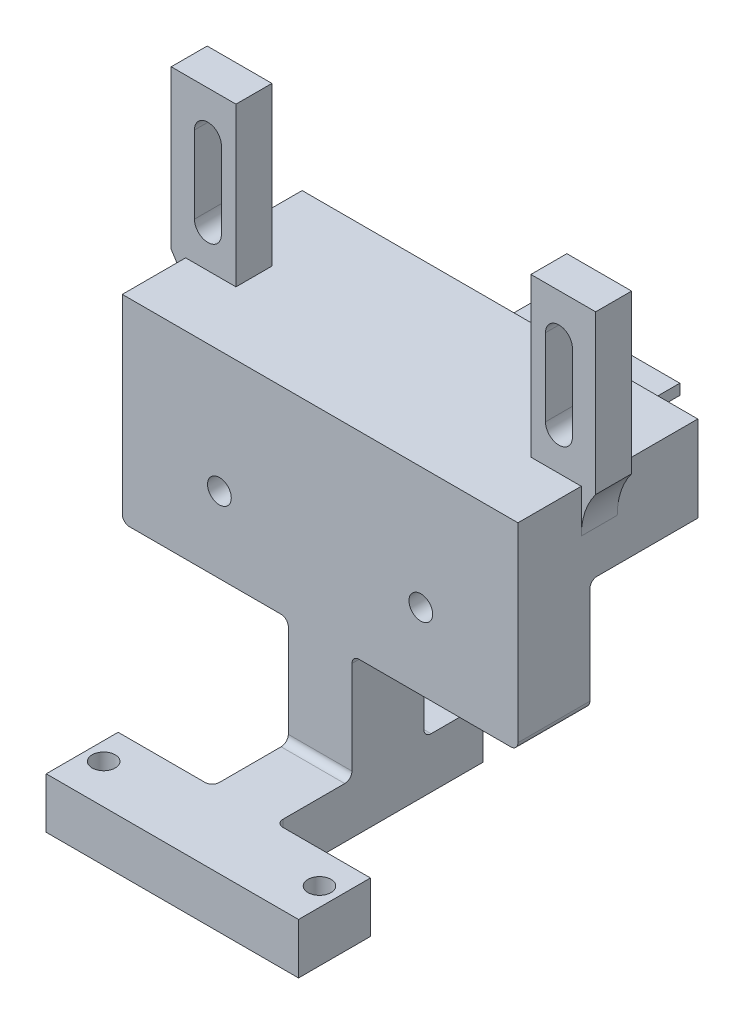
SolidWorks part; units mm, degrees
ref_plane "Front Plane" through (0, 0, 0) normal (0, 0, 1) x (1, 0, 0)
ref_plane "Top Plane" through (0, 0, 0) normal (0, 1, 0) x (1, 0, 0)
ref_plane "Right Plane" through (0, 0, 0) normal (1, 0, 0) x (0, 0, -1)
sketch "草图1" plane through (0, 0, 0) normal (0, 0, 1) x (1, 0, 0)
  line L0 (0, 0) -> (8.5606, 9.7835) construction
  line L1 (-17.5, 20) -> (17.5, 20)
  line L2 (-17.5, 20) -> (-17.5, -20)
  line L3 (-17.5, -20) -> (17.5, -20)
  line L4 (17.5, 20) -> (17.5, -20)
  line L5 (-17.5, 20) -> (0, 0) construction
  line L6 (-17.5, -20) -> (-8.5606, -9.7835) construction
  line L7 (8.5606, -9.7835) -> (17.5, -20) construction
  arc A0 (-12.9135, -1.4975) -> (-8.5606, -9.7835) centre (0, 0) ccw construction
  arc A5 (-1.4975, 12.9135) -> (-12.9135, 1.4975) centre (0, 0) ccw construction
  arc A6 (1.4975, -12.9135) -> (12.9135, -1.4975) centre (0, 0) ccw construction
  arc A8 (12.9135, 1.4975) -> (1.4975, 12.9135) centre (0, 0) ccw construction
  point P0 (0, 0)
  point P19 (0, 0)
  dimension "D1" = 26
  dimension "D2" = 35
  dimension "D3" = 40
extrude "凸台-拉伸1" add sketch "草图1" along normal blind 5
sketch "草图2" plane through (0, 0, 5) normal (0, 0, 1) x (1, 0, 0)
  line L1 (-10, 10) -> (10, 10)
  line L2 (-10, 10) -> (-10, -10)
  line L3 (-10, -10) -> (10, -10)
  line L4 (10, 10) -> (10, -10)
  line L5 (-10, 10) -> (10, -10) construction
  line L6 (-10, -10) -> (10, 10) construction
  point P0 (0, 0)
  dimension "D1" = 20
  dimension "D2" = 20
extrude "凸台-拉伸2" add sketch "草图2" along normal blind 65
sketch "草图3" plane through (-10, 0, 0) normal (-1, 0, 0) x (0, 0, 1)
  line L1 (9.5, -5.5) -> (65.5, -5.5)
  line L2 (65.5, -5.5) -> (65.5, 5.5)
  line L3 (65.5, 5.5) -> (9.5, 5.5)
  line L4 (5, 10) -> (5, -10)
  line L5 (5, -10) -> (70, -10)
  line L6 (70, -10) -> (70, 10)
  line L7 (70, 10) -> (5, 10)
  line L8 (5, 10) -> (5, -10)
  line L9 (5, -10) -> (70, -10)
  line L10 (70, -10) -> (70, 10)
  line L11 (70, 10) -> (5, 10)
  line L12 (9.5, 5.5) -> (5, 5.5)
  line L13 (5, 5.5) -> (5, -5.5)
  line L14 (5, -5.5) -> (9.5, -5.5)
  line L16 (9.5, 5.5) -> (9.5, -5.5) construction
  dimension "D1" = 0
  dimension "D2" = 4.5
extrude "切除-拉伸1" cut sketch "草图3" against normal through all contours L3 L16 L1 L2 | L16 L12 L8 L14
sketch "草图5" plane through (0, 0, 70) normal (0, 0, 1) x (1, 0, 0)
  line L1 (-27.5, 10) -> (27.5, 10)
  line L2 (-27.5, 10) -> (-27.5, -10)
  line L3 (-27.5, -10) -> (27.5, -10)
  line L4 (27.5, 10) -> (27.5, -10)
  line L5 (-27.5, 10) -> (27.5, -10) construction
  line L6 (-27.5, -10) -> (27.5, 10) construction
  point P0 (0, 0)
  dimension "D1" = 20
  dimension "D2" = 55
extrude "凸台-拉伸3" add sketch "草图5" along normal blind 25
sketch "草图6" plane through (0, 0, 95) normal (0, 0, 1) x (1, 0, 0)
  circle A0 centre (-10.5, 24.851) radius 28
  dimension "D1" = 56
sketch "草图7" plane through (0, 0, 95) normal (0, 0, 1) x (1, 0, 0)
  line L0 (-27.5, 0) -> (27.5, 0) construction
  circle A0 centre (-14, 0) radius 1.6
  circle A1 centre (14, 0) radius 1.6
  dimension "D1" = 3.2
  dimension "D2" = 3.2
  dimension "D3" = 14
sketch "草图8" plane through (0, 0, 95) normal (0, 0, 1) x (1, 0, 0)
  line L0 (0, 0) -> (0, 38.7241) construction
  line L1 (17.5, 20) -> (-17.5, 20) construction
  circle A0 centre (0, 20) radius 1.9754 construction
  circle A1 centre (0, 20) radius 14.0625
  dimension "D1" = 28.125
sketch "草图9" plane through (0, 0, 95) normal (0, 0, 1) x (1, 0, 0)
  line L1 (0, -51.5757) -> (0, 13.3029) construction
  line L2 (14, -3.0427) -> (-14, -3.0427) construction
  line L3 (27.5, 10) -> (-27.5, 10) construction
  line L4 (-8.5, -51.5757) -> (8.5, -51.5757) construction
  circle A1 centre (-14, -3.0427) radius 1.65
  circle A2 centre (14, -3.0427) radius 1.65
  dimension "D1" = 14
  dimension "D3" = 3.3
  dimension "D2" = 13.0427
  dimension "D4" = 14
extrude "切除-拉伸3" cut sketch "草图9" against normal blind 27
sketch "草图10" plane through (0, 10, 0) normal (0, 1, 0) x (1, 0, 0)
  line L1 (-27.5, -70) -> (27.5, -70)
  line L2 (-27.5, -70) -> (-27.5, -95)
  line L3 (-27.5, -95) -> (27.5, -95)
  line L4 (27.5, -70) -> (27.5, -95)
extrude "凸台-拉伸4" add sketch "草图10" along normal blind 4.9
sketch "草图11" plane through (0, 14.9, 0) normal (0, 1, 0) x (1, 0, 0)
  line L0 (-27.5, -70) -> (-27.5, -95) construction
  line L1 (-27.5, -81.2) -> (-20.5, -81.2)
  line L2 (-27.5, -81.2) -> (-27.5, -86.2)
  line L3 (-27.5, -86.2) -> (-20.5, -86.2)
  line L4 (-20.5, -81.2) -> (-20.5, -86.2)
  line L5 (-20.5, -94.35) -> (-20.5, -85.7) construction
  line L6 (-25.1, -86.2) -> (-20.5, -86.2) construction
  line L7 (27.5, -95) -> (27.5, -70) construction
  line L8 (27.5, -86.2) -> (20.5, -86.2)
  line L9 (27.5, -86.2) -> (27.5, -81.2)
  line L10 (27.5, -81.2) -> (20.5, -81.2)
  line L11 (20.5, -86.2) -> (20.5, -81.2)
  line L12 (20.5, -65.7) -> (20.5, -85.7) construction
  dimension "D1" = 5
  dimension "D2" = 5
extrude "凸台-拉伸5" add sketch "草图11" along normal blind 21
sketch "草图12" plane through (0, 0, 86.2) normal (0, 0, 1) x (1, 0, 0)
  circle A0 centre (-24.4, 29.9) radius 1.5
  circle A1 centre (-24.4, 19.9) radius 1.5
  circle A2 centre (24.4, 19.9) radius 1.5
  circle A3 centre (24.4, 29.9) radius 1.5
  dimension "D1" = 3
extrude "切除-拉伸4" [suppressed] cut sketch "草图12" against normal blind 21
chamfer "倒角2" distance 10 angle 45 1 edges at (0, -5.5, 65.5)
chamfer "倒角3" distance 3 angle 45 1 edges at (0, 10, 70)
chamfer "倒角4" distance 2 angle 45 1 edges at (0, -10, 5)
sketch "草图13" plane through (0, 0, 5) normal (0, 0, 1) x (1, 0, 0)
  circle A0 centre (0, -13) radius 2.5
  dimension "D1" = 5
sketch "草图14" plane through (27.5, 0, 0) normal (1, 0, 0) x (0, 0, -1)
  circle A0 centre (-79.3333, -5.771) radius 1.5
  circle A1 centre (-65.7124, -5.771) radius 1.5
extrude "切除-拉伸6" [suppressed] cut sketch "草图14" against normal through all
sketch "草图15" plane through (0, 0, 70) normal (0, 0, -1) x (-1, 0, 0)
  line L0 (0, 0) -> (0, -6.8076) construction
  line L1 (10, 13) -> (10, -10) construction
  line L2 (10, 1.9573) -> (29.1308, 1.9573)
  line L3 (10, 1.9573) -> (10, -8.0427)
  line L5 (29.1308, 1.9573) -> (29.1308, -8.0427)
  line L6 (14, -3.0427) -> (8.2324, -3.0427) construction
  line L7 (-14, -3.0427) -> (-8.2324, -3.0427) construction
  line L8 (-29.1308, 1.9573) -> (-29.1308, -8.0427)
  line L10 (-10, 1.9573) -> (-10, -8.0427)
  line L11 (-10, 1.9573) -> (-29.1308, 1.9573)
  line L14 (-29.1308, -8.0427) -> (-29.1308, -10)
  line L15 (-29.1308, -10) -> (-10, -10)
  line L16 (-10, -8.0427) -> (-10, -10)
  line L18 (10, -8.0427) -> (10, -10)
  line L19 (10, -10) -> (29.1308, -10)
  line L20 (29.1308, -8.0427) -> (29.1308, -10)
  point P13 (10, -3.0427)
  dimension "D1" = 10
extrude "切除-拉伸7" cut sketch "草图15" against normal blind 15
sketch "草图16" plane through (-10, 0, 0) normal (-1, 0, 0) x (0, 0, 1)
  line L0 (5, -5.5) -> (55.5, -5.5) construction
  line L1 (5, 5.5) -> (17.9846, 5.5)
  line L2 (5, 5.5) -> (5, -5.5)
  line L3 (5, -5.5) -> (17.9846, -5.5)
  line L4 (17.9846, 5.5) -> (17.9846, -5.5)
extrude "凸台-拉伸6" add sketch "草图16" against normal up to surface (20 mm away) up to face at (10, 0.7242, 45.4231)
chamfer "倒角5" distance 3 angle 45 1 edges at (0, 5.5, 17.9846)
sketch "草图19" plane through (0, 0, 86.2) normal (0, 0, 1) x (1, 0, 0)
  circle A0 centre (-24.4, 29.9) radius 1.6
  circle A1 centre (-24.4, 19.9) radius 1.6
  circle A2 centre (24.4, 19.9) radius 1.6
  circle A3 centre (24.4, 29.9) radius 1.6
  dimension "D1" = 3.2
extrude "切除-拉伸10" cut sketch "草图19" against normal blind 10
fillet "圆角1" radius 5 4 edges at (17.5, 20, 2.5) (17.5, -20, 2.5) (-17.5, -20, 2.5) (-17.5, 20, 2.5)
ref_plane "基准面1" through (0, 0, 0) normal (0, 1, 0) x (1, 0, 0)
sketch "草图20" plane through (-17.5, 0, 0) normal (-1, 0, 0) x (0, 0, 1)
  line L0 (0, 15) -> (0, -15) construction
  line L1 (0, 11.25) -> (5, 11.25)
  line L2 (0, 11.25) -> (0, -11.25)
  line L3 (0, -11.25) -> (5, -11.25)
  line L4 (5, 11.25) -> (5, -11.25)
  line L5 (0, 11.25) -> (-6.5, 11.25) construction
  line L6 (5, 15) -> (5, -15) construction
extrude "凸台-拉伸7" add sketch "草图20" along normal up to surface (17.5 mm away)
sketch "草图21" plane through (-35, 0, 0) normal (-1, 0, 0) x (0, 0, 1)
  line L4 (0, -11.25) -> (5, -11.25)
  line L5 (5, -11.25) -> (5, 11.25)
  line L6 (5, 11.25) -> (0, 11.25)
  line L7 (0, 11.25) -> (0, -11.25)
  line L8 (0, -11.25) -> (5, -11.25)
  line L9 (5, -11.25) -> (5, 11.25)
  line L10 (5, 11.25) -> (0, 11.25)
  line L11 (0, 11.25) -> (0, -11.25)
  dimension "D1" = 0
extrude "凸台-拉伸8" add sketch "草图21" along normal blind 5
sketch "草图22" plane through (0, 0, 0) normal (0, 0, -1) x (-1, 0, 0)
  line L0 (40, 11.25) -> (17.5, 11.25) construction
  line L1 (40, -11.25) -> (35, -11.25)
  line L2 (40, -11.25) -> (40, 11.25)
  line L3 (40, 11.25) -> (35, 11.25)
  line L4 (35, -11.25) -> (35, 11.25)
  line L5 (35, -11.25) -> (35, 11.25) construction
extrude "凸台-拉伸9" add sketch "草图22" along normal blind 10
sketch "草图23" plane through (0, 0, 0) normal (0, 0, -1) x (-1, 0, 0)
  line L0 (35, -11.25) -> (17.5, -11.25) construction
  line L1 (18, -11.25) -> (13, -11.25)
  line L2 (18, -11.25) -> (18, 11.25)
  line L3 (18, 11.25) -> (13, 11.25)
  line L4 (13, -11.25) -> (13, 11.25)
  line L5 (18, -11.25) -> (18, 11.25) construction
  dimension "D1" = 5
extrude "凸台-拉伸10" add sketch "草图23" along normal blind 10
sketch "草图24" plane through (-18, 0, 0) normal (-1, 0, 0) x (0, 0, 1)
  line L1 (-10, 11.25) -> (-6.7, 11.25)
  line L2 (-10, 11.25) -> (-10, -11.25)
  line L3 (-10, -11.25) -> (-6.7, -11.25)
  line L4 (-6.7, 11.25) -> (-6.7, -11.25)
  dimension "D1" = 3.3
extrude "凸台-拉伸11" add sketch "草图24" along normal blind 4
sketch "草图25" plane through (-35, 0, 0) normal (1, 0, 0) x (0, 0, -1)
  line L0 (10, -11.25) -> (0, -11.25) construction
  line L1 (10, 11.25) -> (6.7, 11.25)
  line L2 (10, 11.25) -> (10, -11.25)
  line L3 (10, -11.25) -> (6.7, -11.25)
  line L4 (6.7, 11.25) -> (6.7, -11.25)
  dimension "D1" = 3.3
sketch "草图26" plane through (17.5, 0, 0) normal (1, 0, 0) x (0, 0, -1)
  line L1 (-5, 11.25) -> (0, 11.25)
  line L2 (-5, 11.25) -> (-5, -11.25)
  line L3 (-5, -11.25) -> (0, -11.25)
  line L4 (0, 11.25) -> (0, -11.25)
extrude "凸台-拉伸13" add sketch "草图26" along normal up to surface (17.5 mm away)
sketch "草图27" plane through (35, 0, 0) normal (1, 0, 0) x (0, 0, -1)
  line L4 (-5, -11.25) -> (0, -11.25)
  line L5 (0, -11.25) -> (0, 11.25)
  line L6 (0, 11.25) -> (-5, 11.25)
  line L7 (-5, 11.25) -> (-5, -11.25)
  line L8 (-5, -11.25) -> (0, -11.25)
  line L9 (0, -11.25) -> (0, 11.25)
  line L10 (0, 11.25) -> (-5, 11.25)
  line L11 (-5, 11.25) -> (-5, -11.25)
  dimension "D1" = 0
extrude "凸台-拉伸14" add sketch "草图27" along normal blind 5
sketch "草图28" plane through (0, 0, 0) normal (0, 0, -1) x (-1, 0, 0)
  line L0 (-40, -11.25) -> (-17.5, -11.25) construction
  line L1 (-40, 11.25) -> (-35, 11.25)
  line L2 (-40, 11.25) -> (-40, -11.25)
  line L3 (-40, -11.25) -> (-35, -11.25)
  line L4 (-35, 11.25) -> (-35, -11.25)
  line L5 (-35, -11.25) -> (-35, 11.25) construction
extrude "凸台-拉伸15" add sketch "草图28" along normal up to surface (10 mm away) up to face at (-17.5, 0, -10)
sketch "草图29" plane through (0, 0, 0) normal (0, 0, -1) x (-1, 0, 0)
  line L0 (-35, 11.25) -> (-17.5, 11.25) construction
  line L1 (-18, 11.25) -> (-13, 11.25)
  line L2 (-18, 11.25) -> (-18, -11.25)
  line L3 (-18, -11.25) -> (-13, -11.25)
  line L4 (-13, 11.25) -> (-13, -11.25)
  line L5 (-18, -11.25) -> (-18, 11.25) construction
  line L6 (-35, -11.25) -> (-17.5, -11.25) construction
  dimension "D1" = 5
extrude "凸台-拉伸16" add sketch "草图29" along normal up to surface (10 mm away) up to face at (37.5, 0, -10)
sketch "草图30" plane through (35, 0, 0) normal (-1, 0, 0) x (0, 0, 1)
  line L0 (-10, -11.25) -> (0, -11.25) construction
  line L1 (-10, 11.25) -> (-6.6, 11.25)
  line L2 (-10, 11.25) -> (-10, -11.25)
  line L3 (-10, -11.25) -> (-6.6, -11.25)
  line L4 (-6.6, 11.25) -> (-6.6, -11.25)
  dimension "D1" = 3.4
sketch "草图31" plane through (18, 0, 0) normal (1, 0, 0) x (0, 0, -1)
  line L0 (10, 11.25) -> (0, 11.25) construction
  line L1 (10, -11.25) -> (6.6, -11.25)
  line L2 (10, -11.25) -> (10, 11.25)
  line L3 (10, 11.25) -> (6.6, 11.25)
  line L4 (6.6, -11.25) -> (6.6, 11.25)
  dimension "D1" = 3.4
extrude "凸台-拉伸18" add sketch "草图31" along normal blind 4
sketch "草图32" plane through (0, 0, 5) normal (0, 0, 1) x (1, 0, 0)
  circle A0 centre (-32.5, 3.75) radius 1
  circle A1 centre (-32.5, -4.25) radius 1
  circle A2 centre (-20.5, 3.75) radius 1
  circle A3 centre (-20.5, -4.25) radius 1
  circle A4 centre (20.5, 3.75) radius 1
  circle A5 centre (20.5, -4.25) radius 1
  circle A6 centre (32.5, -4.25) radius 1
  circle A7 centre (32.5, 3.75) radius 1
  dimension "D1" = 2
  dimension "D2" = 2
  dimension "D3" = 2
sketch "草图33" plane through (0, -10, 0) normal (0, -1, 0) x (1, 0, 0)
  line L0 (-27.5, 70) -> (-27.5, 85) construction
  line L1 (-27.5, 62.1642) -> (27.5, 62.1642)
  line L2 (-27.5, 62.1642) -> (-27.5, 106.0669)
  line L3 (-27.5, 106.0669) -> (27.5, 106.0669)
  line L4 (27.5, 62.1642) -> (27.5, 106.0669)
extrude "凸台-拉伸19" [suppressed] add sketch "草图33" along normal up to surface (25.5757 mm away)
sketch "草图34" [suppressed] plane through (0, -10, 0) normal (0, 1, 0) x (1, 0, 0)
  line L0 (0, -106.0669) -> (0, -40) construction
  line L1 (27.5, -106.0669) -> (-27.5, -106.0669) construction
  line L2 (27.5, -40) -> (-27.5, -40) construction
  line L4 (-27.5, -40) -> (-6, -40)
  line L5 (-27.5, -40) -> (-27.5, -77.2915)
  line L6 (-27.5, -77.2915) -> (-6, -77.2915)
  line L7 (-6, -40) -> (-6, -77.2915)
  line L8 (27.5, -40) -> (6, -40)
  line L9 (27.5, -40) -> (27.5, -77.2915)
  line L10 (27.5, -77.2915) -> (6, -77.2915)
  line L11 (6, -40) -> (6, -77.2915)
  line L12 (27.5, -106.0669) -> (-27.5, -106.0669)
  line L13 (27.5, -106.0669) -> (27.5, -65)
  line L14 (27.5, -65) -> (-27.5, -65)
  line L15 (-27.5, -106.0669) -> (-27.5, -65)
  dimension "D1" = 6
  dimension "D2" = 6
extrude "切除-拉伸12" [suppressed] cut sketch "草图34" against normal blind 18
sketch "草图35" [suppressed] plane through (0, -35.5757, 0) normal (0, -1, 0) x (1, 0, 0)
  line L0 (-17.5, 85.6) -> (-17.5, 41.6) construction
  line L1 (-27.5, 62.1642) -> (-4.8154, 62.1642)
  line L2 (-27.5, 62.1642) -> (-27.5, 81.8991)
  line L3 (-17.5, 81.8991) -> (-4.8154, 81.8991)
  line L4 (-4.8154, 62.1642) -> (-4.8154, 81.8991)
  line L5 (27.5, 62.1642) -> (3.7618, 62.1642)
  line L6 (27.5, 62.1642) -> (27.5, 81.8624)
  line L7 (17.5, 81.8991) -> (3.7618, 81.8991)
  line L8 (3.7618, 62.1642) -> (3.7618, 81.8991)
  line L9 (-27.5, 106.0669) -> (-17.5, 106.0669)
  line L10 (-27.5, 106.0669) -> (-27.5, 81.8991)
  line L12 (-17.5, 106.0669) -> (-17.5, 81.8991)
  line L14 (27.5, 106.0669) -> (17.5, 106.0669)
  line L17 (17.5, 106.0669) -> (17.5, 81.8991)
  line L19 (27.5, 81.8624) -> (27.5, 106.0669)
extrude "切除-拉伸13" [suppressed] cut sketch "草图35" against normal blind 11
sketch "草图36" [suppressed] plane through (0, -35.5757, 0) normal (0, -1, 0) x (1, 0, 0)
  line L0 (17.5, 106.0669) -> (17.5, 81.8991) construction
  line L1 (-17.5, 81.8991) -> (17.5, 81.8991)
  line L2 (-17.5, 81.8991) -> (-17.5, 95.6286)
  line L3 (-17.5, 95.6286) -> (17.5, 95.6286)
  line L4 (17.5, 81.8991) -> (17.5, 95.6286)
extrude "切除-拉伸14" [suppressed] cut sketch "草图36" against normal blind 5
sketch "草图37" [suppressed] plane through (0, -35.5757, 0) normal (0, -1, 0) x (1, 0, 0)
  line L0 (3.7618, 81.8991) -> (3.7618, 62.1642) construction
  line L1 (-4.8154, 62.1642) -> (3.7618, 62.1642)
  line L2 (-4.8154, 62.1642) -> (-4.8154, 72.6172)
  line L3 (-4.8154, 72.6172) -> (3.7618, 72.6172)
  line L4 (3.7618, 62.1642) -> (3.7618, 72.6172)
extrude "切除-拉伸15" [suppressed] cut sketch "草图37" against normal up to surface (5 mm away)
fillet "圆角2" [suppressed] radius 1
sketch "草图38" [suppressed] plane through (0, -28, 0) normal (0, 1, 0) x (1, 0, 0)
  circle A0 centre (-15, -80.1116) radius 1.5
  circle A1 centre (15, -80.1116) radius 1.5
extrude "切除-拉伸16" [suppressed] cut sketch "草图38" against normal up to surface (7.5757 mm away)
sketch "草图39" plane through (-17.5, 0, 0) normal (-1, 0, 0) x (0, 0, 1)
  line L1 (0, 11.25) -> (7.1368, 11.25)
  line L2 (0, 11.25) -> (0, 24.7683)
  line L3 (0, 24.7683) -> (7.1368, 24.7683)
  line L4 (7.1368, 11.25) -> (7.1368, 24.7683)
  line L5 (0, -11.25) -> (8.1393, -11.25)
  line L6 (0, -11.25) -> (0, -21.7723)
  line L7 (0, -21.7723) -> (8.1393, -21.7723)
  line L8 (8.1393, -11.25) -> (8.1393, -21.7723)
extrude "切除-拉伸17" cut sketch "草图39" against normal up to surface (35 mm away) up to face at (17.5, 13.125, 2.5)
sketch "草图40" plane through (0, -10, 0) normal (0, -1, 0) x (1, 0, 0)
  line L1 (27.5, 85) -> (-27.5, 85)
  line L2 (27.5, 85) -> (27.5, 95)
  line L3 (27.5, 95) -> (-27.5, 95)
  line L4 (-27.5, 85) -> (-27.5, 95)
extrude "凸台-拉伸20" add sketch "草图40" along normal up to surface (25.5757 mm away)
sketch "草图41" plane through (0, 0, 95) normal (0, 0, 1) x (1, 0, 0)
  line L0 (27.5, -35.5757) -> (-27.5, -35.5757) construction
  line L1 (-4.4244, -35.5757) -> (4.4244, -35.5757)
  line L2 (-4.4244, -35.5757) -> (-4.4244, -28.5296)
  line L3 (-4.4244, -28.5296) -> (4.4244, -28.5296)
  line L4 (4.4244, -35.5757) -> (4.4244, -28.5296)
  line L5 (4.4244, -35.5757) -> (-4.4244, -28.5296) construction
  line L6 (0, -37.5757) -> (0, -41.8305) construction
  line L7 (-8.5, -37.5757) -> (8.5, -37.5757) construction
  point P11 (0, -32.0526)
extrude "凸台-拉伸21" add sketch "草图41" along normal up to surface (20.578 mm away)
sketch "草图42" plane through (-4.4244, 0, 0) normal (-1, 0, 0) x (0, 0, 1)
  line L0 (115.578, -28.5296) -> (95, -28.5296) construction
  line L1 (115.578, -35.5757) -> (76.7852, -35.5757)
  line L2 (115.578, -35.5757) -> (115.578, -28.5296)
  line L3 (115.578, -28.5296) -> (76.7852, -28.5296)
  line L4 (76.7852, -35.5757) -> (76.7852, -28.5296)
extrude "凸台-拉伸22" add sketch "草图42" along normal up to surface (13.0756 mm away) and the other way blind 22
sketch "草图43" plane through (0, -35.5757, 0) normal (0, -1, 0) x (1, 0, 0)
  line L1 (27.5, 76.7852) -> (4.4244, 76.7852)
  line L2 (27.5, 76.7852) -> (27.5, 105.578)
  line L3 (27.5, 105.578) -> (4.4244, 105.578)
  line L4 (4.4244, 76.7852) -> (4.4244, 105.578)
  line L6 (-27.5, 76.7852) -> (-4.4244, 76.7852)
  line L7 (-27.5, 76.7852) -> (-27.5, 105.578)
  line L8 (-27.5, 105.578) -> (-4.4244, 105.578)
  line L9 (-4.4244, 76.7852) -> (-4.4244, 105.578)
  line L11 (17.5756, 76.7852) -> (-17.5, 76.7852) construction
  line L13 (17.5756, 115.578) -> (-17.5, 115.578) construction
  dimension "D1" = 10
extrude "切除-拉伸18" cut sketch "草图43" against normal blind 22
fillet "圆角3" radius 1 11 edges at (-27.5, -13.5757, 90) (27.5, -13.5757, 90) (4.4244, -13.5757, 90) (18.75, 1.9573, 85) (-4.4244, -13.5757, 90) (0, -10, 85) (-18.75, 1.9573, 85) (0, -28.5296, 95) (0, -28.5296, 85) (-4.4244, -32.0526, 105.578) (4.4244, -32.0526, 105.578)
sketch "草图46" plane through (0, 0, 0) normal (0, 0, -1) x (-1, 0, 0)
  line L0 (-13, -11.25) -> (13, -11.25) construction
  line L1 (-13, 11.25) -> (-3.7618, 11.25)
  line L2 (-13, 11.25) -> (-13, -11.25)
  line L3 (-13, -11.25) -> (-3.7618, -11.25)
  line L4 (-3.7618, 11.25) -> (-3.7618, -11.25)
extrude "凸台-拉伸26" add sketch "草图46" along normal blind 10
sketch "草图47" plane through (0, 0, -10) normal (0, 0, -1) x (-1, 0, 0)
  line L0 (0, 120.494) -> (0, -21.6004) construction
  line L1 (-3.7618, 11.25) -> (-22, 11.25) construction
  line L2 (-8.0664, 11.25) -> (-10.7005, 11.25)
  line L3 (-10.7005, 11.25) -> (-10.7005, -11.25)
  line L4 (-22, -11.25) -> (-3.7618, -11.25) construction
  line L5 (-10.7005, -11.25) -> (-6.3328, -11.25)
  line L6 (-6.3328, -11.25) -> (-6.3328, -9.5796) construction
  line L7 (-8.0664, -7.9) -> (-8.0664, -8.75)
  line L8 (-8.0664, -2.9) -> (-8.0664, -3.75)
  line L9 (-8.0664, 7.1) -> (-8.0664, 6.25)
  line L10 (-8.0664, 2.1) -> (-8.0664, 1.25)
  circle A0 centre (0, 109.494) radius 11 construction
  arc A1 (-8.0664, 11.25) -> (-8.0664, 7.1) centre (-8.3894, 9.175) cw
  arc A2 (-8.0664, 6.25) -> (-8.0664, 2.1) centre (-8.3894, 4.175) cw
  arc A3 (-8.0664, 1.25) -> (-8.0664, -2.9) centre (-8.3894, -0.825) cw
  arc A4 (-8.0664, -3.75) -> (-8.0664, -7.9) centre (-8.3894, -5.825) cw
  arc A5 (-8.0664, -8.75) -> (-6.3328, -11.25) centre (-8.3894, -10.825) cw
  dimension "D1" = 2.1
  dimension "D2" = 5
extrude "切除-拉伸19" cut sketch "草图47" against normal blind 10
sketch "草图48" plane through (0, -28.5296, 0) normal (0, 1, 0) x (1, 0, 0)
  circle A0 centre (15, -110.0896) radius 1.6
  circle A1 centre (-15, -110.0896) radius 1.6
  dimension "D1" = 3.2
extrude "切除-拉伸20" cut sketch "草图48" against normal blind 10
sketch "草图49" plane through (0, 0, 86.2) normal (0, 0, 1) x (1, 0, 0)
  line L0 (0, 0) -> (0, 23.1634) construction
  line L1 (-24.4, 29.9) -> (-24.4, 19.1657) construction
  line L2 (-22.5287, 29.9) -> (-22.5287, 19.1657)
  line L3 (-26.2713, 29.9) -> (-26.2713, 19.1657)
  line L4 (24.4, 29.9) -> (24.4, 19.1657) construction
  line L5 (22.5287, 29.9) -> (22.5287, 19.1657)
  line L6 (26.2713, 29.9) -> (26.2713, 19.1657)
  arc A0 (-22.5287, 29.9) -> (-26.2713, 29.9) centre (-24.4, 29.9) ccw
  arc A1 (-26.2713, 19.1657) -> (-22.5287, 19.1657) centre (-24.4, 19.1657) ccw
  arc A2 (22.5287, 29.9) -> (26.2713, 29.9) centre (24.4, 29.9) cw
  arc A3 (26.2713, 19.1657) -> (22.5287, 19.1657) centre (24.4, 19.1657) cw
  point P6 (-24.4, 24.5328)
  point P13 (24.4, 24.5328)
extrude "切除-拉伸21" cut sketch "草图49" against normal blind 10
sketch "草图50" plane through (0, 0, -10) normal (0, 0, -1) x (-1, 0, 0)
  line L0 (-22, -11.25) -> (-10.7005, -11.25) construction
  line L1 (-3.7618, 11.25) -> (-6.3328, 11.25)
  line L2 (-3.7618, 11.25) -> (-3.7618, -11.25)
  line L3 (-3.7618, -11.25) -> (-6.3328, -11.25)
  line L4 (-6.3328, 11.25) -> (-6.3328, -11.25)
  line L5 (-10.7005, 11.25) -> (-13.5656, 11.25)
  line L6 (-10.7005, 11.25) -> (-10.7005, -11.25)
  line L7 (-10.7005, -11.25) -> (-13.5656, -11.25)
  line L8 (-13.5656, 11.25) -> (-13.5656, -11.25)
extrude "凸台-拉伸27" add sketch "草图50" along normal blind 10
sketch "草图53" plane through (0, 11.25, 0) normal (0, 1, 0) x (1, 0, 0)
  line L1 (8.0664, 10) -> (3.7618, 10)
  line L2 (8.0664, 10) -> (8.0664, 0)
  line L3 (8.0664, 0) -> (3.7618, 0)
  line L4 (3.7618, 10) -> (3.7618, 0)
  line L5 (13.5656, 10) -> (10.7005, 10)
  line L6 (13.5656, 10) -> (13.5656, 0)
  line L7 (13.5656, 0) -> (10.7005, 0)
  line L8 (10.7005, 10) -> (10.7005, 0)
extrude "凸台-拉伸28" add sketch "草图53" along normal blind 11
sketch "草图51" plane through (13.5656, 0, 0) normal (1, 0, 0) x (0, 0, -1)
  line L0 (15, 11.25) -> (15, -11.25) construction
  line L1 (20, 11.25) -> (10, 11.25) construction
  line L2 (20, -11.25) -> (10, -11.25) construction
  line L3 (20, 11.25) -> (20, -11.25) construction
  circle A0 centre (16, 6.25) radius 1.6
  circle A1 centre (16, -6.25) radius 1.6
  dimension "D1" = 3.2
  dimension "D2" = 5
  dimension "D3" = 5
  dimension "D4" = 4
extrude "切除-拉伸22" cut sketch "草图51" against normal blind 12
sketch "草图52" plane through (0, 11.25, 0) normal (0, 1, 0) x (1, 0, 0)
  line L0 (-26.5, 0) -> (-26.5, 6.7) construction
  line L1 (-35, 0) -> (-18, 0) construction
  line L2 (0, 0) -> (0, 4.3666) construction
  line L3 (-35.1, 6.75) -> (-17.9, 6.75)
  line L4 (-35.1, 6.75) -> (-35.1, -0.05)
  line L5 (-35.1, -0.05) -> (-17.9, -0.05)
  line L6 (-17.9, 6.75) -> (-17.9, -0.05)
  line L7 (-35.1, 6.75) -> (-17.9, -0.05) construction
  line L8 (-35.1, -0.05) -> (-17.9, 6.75) construction
  line L9 (35.1, -0.05) -> (17.9, -0.05)
  line L10 (17.9, 6.75) -> (17.9, -0.05)
  line L11 (35.1, 6.75) -> (17.9, 6.75)
  line L12 (35.1, 6.75) -> (35.1, -0.05)
  point P4 (-26.5, 3.35)
  dimension "D1" = 17.2
  dimension "D2" = 6.8
extrude "切除-拉伸23" cut sketch "草图52" against normal blind 39
ref_plane "基准面2" through (5.0473, 0, 0) normal (-1, 0, 0) x (0, 0, 1)
sketch "草图54" plane through (0, 0, -10) normal (0, 0, -1) x (-1, 0, 0)
  line L0 (-8.0664, 21.25) -> (-10.7005, 21.25)
  line L1 (-10.7005, 21.25) -> (-10.7005, -1.25)
  line L2 (-10.7005, -1.25) -> (-6.3328, -1.25)
  line L3 (-8.0664, 1.25) -> (-8.0664, 2.1)
  line L4 (-8.0664, 6.25) -> (-8.0664, 7.1)
  line L5 (-8.0664, 11.25) -> (-8.0664, 12.1)
  line L6 (-8.0664, 16.25) -> (-8.0664, 17.1)
  line L7 (-8.0664, 11.25) -> (-10.7005, 11.25)
  line L8 (-10.7005, 11.25) -> (-10.7005, -11.25)
  line L10 (-8.0664, -8.75) -> (-8.0664, -7.9)
  line L11 (-8.0664, -3.75) -> (-8.0664, -2.9)
  line L12 (-8.0664, 1.25) -> (-8.0664, 2.1)
  line L13 (-8.0664, 6.25) -> (-8.0664, 7.1)
  line L15 (-10.7005, 11.25) -> (-10.7005, -11.25)
  line L17 (-8.0664, -8.75) -> (-8.0664, -7.9)
  line L18 (-8.0664, -3.75) -> (-8.0664, -2.9)
  line L19 (-8.0664, 1.25) -> (-8.0664, 2.1)
  line L20 (-8.0664, 6.25) -> (-8.0664, 7.1)
  line L48 (-8.0664, 11.25) -> (-10.7005, 11.25)
  line L50 (-10.7005, -11.25) -> (-6.3328, -11.25)
  line L51 (-10.7005, -11.25) -> (-6.3328, -11.25)
  arc A0 (-8.0664, 17.1) -> (-8.0664, 21.25) centre (-8.3894, 19.175) ccw
  arc A1 (-6.3328, -1.25) -> (-8.0664, 1.25) centre (-8.3894, -0.825) ccw
  arc A2 (-8.0664, 2.1) -> (-8.0664, 6.25) centre (-8.3894, 4.175) ccw
  arc A3 (-8.0664, 7.1) -> (-8.0664, 11.25) centre (-8.3894, 9.175) ccw
  arc A4 (-8.0664, 12.1) -> (-8.0664, 16.25) centre (-8.3894, 14.175) ccw
  arc A5 (-8.0664, 7.1) -> (-8.0664, 11.25) centre (-8.3894, 9.175) ccw
  arc A6 (-6.3328, -11.25) -> (-8.0664, -8.75) centre (-8.3894, -10.825) ccw
  arc A7 (-8.0664, -7.9) -> (-8.0664, -3.75) centre (-8.3894, -5.825) ccw
  arc A8 (-8.0664, -2.9) -> (-8.0664, 1.25) centre (-8.3894, -0.825) ccw
  arc A9 (-8.0664, 2.1) -> (-8.0664, 6.25) centre (-8.3894, 4.175) ccw
  arc A10 (-8.0664, 7.1) -> (-8.0664, 11.25) centre (-8.3894, 9.175) ccw
  arc A11 (-6.3328, -11.25) -> (-8.0664, -8.75) centre (-8.3894, -10.825) ccw
  arc A12 (-8.0664, -7.9) -> (-8.0664, -3.75) centre (-8.3894, -5.825) ccw
  arc A13 (-8.0664, -2.9) -> (-8.0664, 1.25) centre (-8.3894, -0.825) ccw
  arc A14 (-8.0664, 2.1) -> (-8.0664, 6.25) centre (-8.3894, 4.175) ccw
  line M30 (-8.0664, 22.25) -> (-8.0664, 11.25)
  dimension "D1" = 0
  dimension "D2" = 2
extrude "切除-拉伸24" cut sketch "草图54" against normal blind 10 contours A4 M30 | A0 M30
sketch "草图55" plane through (0, 0, 5) normal (0, 0, 1) x (1, 0, 0)
  line L0 (-40, 11.25) -> (40, 11.25) construction
  line L5 (-16, -11.25) -> (16, -11.25)
  line L6 (-16, -11.25) -> (-16, 11.25)
  line L7 (-16, 11.25) -> (16, 11.25)
  line L8 (16, -11.25) -> (16, 11.25)
  line L10 (-40, -11.25) -> (-40, 11.25) construction
  line L11 (40, 11.25) -> (40, -11.25) construction
  dimension "D1" = 24
  dimension "D2" = 24
extrude "凸台-拉伸29" add sketch "草图55" along normal blind 12
sketch "草图56" plane through (0, 0, 0) normal (0, 0, -1) x (-1, 0, 0)
  line L0 (-3.7618, -11.25) -> (13, -11.25) construction
  line L1 (13, 11.25) -> (2.6989, 11.25)
  line L2 (13, 11.25) -> (13, -11.25)
  line L3 (13, -11.25) -> (2.6989, -11.25)
  line L4 (2.6989, 11.25) -> (2.6989, -11.25)
extrude "切除-拉伸25" cut sketch "草图56" against normal blind 7
sketch "草图57" plane through (0, 11.25, 0) normal (0, 1, 0) x (1, 0, 0)
  line L0 (-40, -5) -> (-16, -5) construction
  line L2 (-19.9654, -5) -> (-19.9654, -0.05)
  line L4 (-33.1654, -5) -> (-33.1654, -0.05)
  line L5 (-35.1, -0.05) -> (-17.9, -0.05) construction
  line L6 (-16.9654, -5) -> (-16.9654, -0.05)
  line L8 (-36.1654, -5) -> (-36.1654, -0.05)
  line L10 (-16.9654, -5) -> (-19.9654, -5)
  line L11 (-33.1654, -5) -> (-36.1654, -5)
  line L12 (-33.1654, -0.05) -> (-36.1654, -0.05)
  line L13 (-19.9654, -0.05) -> (-16.9654, -0.05)
  line L14 (-16.9654, -8) -> (-16.9654, 2.95) construction
  line L15 (-16.9654, 2.95) -> (-36.1654, 2.95) construction
  line L16 (-19.9654, -5) -> (-33.1654, -5) construction
  line L17 (-19.9654, -0.05) -> (-33.1654, -0.05) construction
  line L18 (-36.1654, -8) -> (-36.1654, 2.95) construction
  line L19 (-16.9654, -8) -> (-36.1654, -8) construction
  dimension "D1" = 13.2
  dimension "D2" = 3
extrude "凸台-拉伸30" add sketch "草图57" along normal blind 8
sketch "草图58" plane through (0, 0, -10) normal (0, 0, -1) x (-1, 0, 0)
  line L1 (13, 11.25) -> (22, 11.25)
  line L2 (13, 11.25) -> (13, -11.25)
  line L3 (13, -11.25) -> (22, -11.25)
  line L4 (22, 11.25) -> (22, -11.25)
  line L5 (-22, 11.25) -> (-13.5656, 11.25)
  line L6 (-22, 11.25) -> (-22, -11.25)
  line L7 (-22, -11.25) -> (-13.5656, -11.25)
  line L8 (-13.5656, 11.25) -> (-13.5656, -11.25)
extrude "切除-拉伸26" cut sketch "草图58" against normal up to surface (10.05 mm away) up to face at (-26.5436, 10.1667, 0.05)
sketch "草图59" plane through (0, 14.9, 0) normal (0, 1, 0) x (1, 0, 0)
  line L12 (20.5, -86.2) -> (20.5, -81.2)
  line L13 (20.5, -81.2) -> (27.5, -81.2)
  line L14 (27.5, -81.2) -> (27.5, -70)
  line L15 (27.5, -70) -> (-27.5, -70)
  line L16 (-27.5, -70) -> (-27.5, -81.2)
  line L17 (-27.5, -81.2) -> (-20.5, -81.2)
  line L18 (-20.5, -81.2) -> (-20.5, -86.2)
  line L19 (-20.5, -86.2) -> (-27.5, -86.2)
  line L20 (-27.5, -86.2) -> (-27.5, -95)
  line L21 (-27.5, -95) -> (27.5, -95)
  line L22 (27.5, -95) -> (27.5, -86.2)
  line L23 (27.5, -86.2) -> (20.5, -86.2)
  line L24 (20.5, -86.2) -> (20.5, -81.2)
  line L25 (20.5, -81.2) -> (27.5, -81.2)
  line L26 (27.5, -81.2) -> (27.5, -70)
  line L27 (27.5, -70) -> (-27.5, -70)
  line L28 (-27.5, -70) -> (-27.5, -81.2)
  line L29 (-27.5, -81.2) -> (-20.5, -81.2)
  line L30 (-20.5, -81.2) -> (-20.5, -86.2)
  line L31 (-20.5, -86.2) -> (-27.5, -86.2)
  line L32 (-27.5, -86.2) -> (-27.5, -95)
  line L33 (-27.5, -95) -> (27.5, -95)
  line L34 (27.5, -95) -> (27.5, -86.2)
  line L35 (27.5, -86.2) -> (20.5, -86.2)
  dimension "D1" = 0
extrude "切除-拉伸27" cut sketch "草图59" against normal blind 1
sketch "草图60" plane through (0, 0, 5) normal (0, 0, 1) x (1, 0, 0)
  line L0 (-40, -11.25) -> (-16, -11.25) construction
  line L1 (-16, 11.25) -> (-18.55, 11.25)
  line L2 (-16, 11.25) -> (-16, -11.25)
  line L3 (-16, -11.25) -> (-18.55, -11.25)
  line L4 (-18.55, 11.25) -> (-18.55, -11.25)
  line L5 (16, -11.25) -> (16, 11.25) construction
  line L6 (16, 11.25) -> (18.55, 11.25)
  line L7 (16, 11.25) -> (16, -11.25)
  line L8 (16, -11.25) -> (18.55, -11.25)
  line L9 (18.55, 11.25) -> (18.55, -11.25)
  line L10 (16, 11.25) -> (-16, 11.25) construction
  line L11 (40, -11.25) -> (16, -11.25) construction
  dimension "D1" = 2.55
  dimension "D2" = 2.55
extrude "凸台-拉伸31" add sketch "草图60" along normal up to surface (12 mm away) up to face at (0, 0, 17)
sketch "草图61" plane through (0, 0, 0.05) normal (0, 0, -1) x (-1, 0, 0)
  line L0 (35.1, -11.25) -> (13, -11.25) construction
  line L1 (13, 11.25) -> (16.9654, 11.25)
  line L2 (13, 11.25) -> (13, -11.25)
  line L3 (13, -11.25) -> (16.9654, -11.25)
  line L4 (16.9654, 11.25) -> (16.9654, -11.25)
  line L5 (16.9654, 19.25) -> (16.9654, 11.25) construction
extrude "切除-拉伸28" cut sketch "草图61" against normal up to surface (6.95 mm away) up to face at (-7.8494, 0, 7)
sketch "草图62" plane through (-27.5, 0, 0) normal (-1, 0, 0) x (0, 0, 1)
  line L1 (81.2, 35.9) -> (86.2, 35.9)
  line L2 (81.2, 35.9) -> (81.2, 13.9)
  line L3 (81.2, 13.9) -> (86.2, 13.9)
  line L4 (86.2, 35.9) -> (86.2, 13.9)
extrude "凸台-拉伸32" add sketch "草图62" along normal blind 2
sketch "草图63" plane through (27.5, 0, 0) normal (1, 0, 0) x (0, 0, -1)
  line L1 (-86.2, 35.9) -> (-81.2, 35.9)
  line L2 (-86.2, 35.9) -> (-86.2, 13.9)
  line L3 (-86.2, 13.9) -> (-81.2, 13.9)
  line L4 (-81.2, 35.9) -> (-81.2, 13.9)
extrude "凸台-拉伸33" add sketch "草图63" along normal blind 2
fillet "圆角4" [suppressed] radius 10
sketch "草图64" plane through (0, 0, -10) normal (0, 0, -1) x (-1, 0, 0)
  line L4 (-35, 11.25) -> (-40, 11.25)
  line L5 (-40, 11.25) -> (-40, -11.25)
  line L6 (-40, -11.25) -> (-35, -11.25)
  line L7 (-35, -11.25) -> (-35, 11.25)
  line L8 (-35, 11.25) -> (-40, 11.25)
  line L9 (-40, 11.25) -> (-40, -11.25)
  line L10 (-40, -11.25) -> (-35, -11.25)
  line L11 (-35, -11.25) -> (-35, 11.25)
  dimension "D1" = 0
extrude "凸台-拉伸34" add sketch "草图64" along normal blind 8
sketch "草图65" plane through (0, 0, -18) normal (0, 0, -1) x (-1, 0, 0)
  line L1 (-35, 11.25) -> (-35.1, 11.25)
  line L2 (-35, 11.25) -> (-35, -11.25)
  line L3 (-35, -11.25) -> (-35.1, -11.25)
  line L4 (-35.1, 11.25) -> (-35.1, -11.25)
extrude "切除-拉伸30" cut sketch "草图65" against normal blind 15
sketch "草图66" plane through (0, 0, -10) normal (0, 0, -1) x (-1, 0, 0)
  line L1 (40, 11.25) -> (35, 11.25)
  line L2 (40, 11.25) -> (40, -11.25)
  line L3 (40, -11.25) -> (35, -11.25)
  line L4 (35, 11.25) -> (35, -11.25)
extrude "凸台-拉伸35" add sketch "草图66" along normal blind 8
sketch "草图67" plane through (40, 0, 0) normal (1, 0, 0) x (0, 0, -1)
  circle A0 centre (2.45, 4.25) radius 1.1
  circle A1 centre (2.45, -3.75) radius 1.1
  circle A2 centre (14.45, -3.75) radius 1.1
  circle A3 centre (14.45, 4.25) radius 1.1
  dimension "D1" = 2.2
extrude "切除-拉伸31" cut sketch "草图67" against normal blind 9
mirror "镜向1" about plane through (0, 0, 0) normal (1, 0, 0) of "切除-拉伸31"
sketch "草图68" plane through (0, 0, -18) normal (0, 0, -1) x (-1, 0, 0)
  line L1 (35, 11.25) -> (35.1, 11.25)
  line L2 (35, 11.25) -> (35, -11.25)
  line L3 (35, -11.25) -> (35.1, -11.25)
  line L4 (35.1, 11.25) -> (35.1, -11.25)
extrude "切除-拉伸32" cut sketch "草图68" against normal blind 12
sketch "草图69" plane through (-18.55, 0, 0) normal (-1, 0, 0) x (0, 0, 1)
  line L4 (5, -11.25) -> (17, -11.25)
  line L5 (17, -11.25) -> (17, 11.25)
  line L6 (17, 11.25) -> (5, 11.25)
  line L7 (5, 11.25) -> (5, -11.25)
  line L8 (5, -11.25) -> (17, -11.25)
  line L9 (17, -11.25) -> (17, 11.25)
  line L10 (17, 11.25) -> (5, 11.25)
  line L11 (5, 11.25) -> (5, -11.25)
  dimension "D1" = 0
extrude "凸台-拉伸36" add sketch "草图69" along normal blind 5
sketch "草图70" plane through (0, 0, 70) normal (0, 0, -1) x (-1, 0, 0)
  line L1 (-53.864, 37.5331) -> (53.864, 37.5331)
  line L2 (-53.864, 37.5331) -> (-53.864, -37.5331)
  line L3 (-53.864, -37.5331) -> (53.864, -37.5331)
  line L4 (53.864, 37.5331) -> (53.864, -37.5331)
  line L5 (-53.864, 37.5331) -> (53.864, -37.5331) construction
  line L6 (-53.864, -37.5331) -> (53.864, 37.5331) construction
  point P0 (0, 0)
extrude "切除-拉伸33" cut sketch "草图70" along normal blind 130
sketch "草图73" plane through (0, 0, 70) normal (0, 0, -1) x (-1, 0, 0)
  line L0 (0, 1.9573) -> (0, -10) construction
  line L2 (-10, -10) -> (10, -10) construction
  line L3 (-10, 1.9573) -> (10, 1.9573) construction
  line L4 (10, 1.9573) -> (27.5, 1.9573) construction
  line L5 (27.5, 1.9573) -> (10, 1.9573) construction
  line L7 (-3.35, 0.4786) -> (3.35, 0.4786)
  line L8 (-3.35, 0.4786) -> (-3.35, -8.5214)
  line L9 (-3.35, -8.5214) -> (3.35, -8.5214)
  line L10 (3.35, 0.4786) -> (3.35, -8.5214)
  line L11 (-3.35, 0.4786) -> (3.35, -8.5214) construction
  line L12 (-3.35, -8.5214) -> (3.35, 0.4786) construction
  point P2 (0, -4.0214)
  dimension "D1" = 6.7
  dimension "D2" = 9
extrude "切除-拉伸34" cut sketch "草图73" against normal blind 15
fillet "圆角5" radius 10 2 edges at (-27.5, 13.9, 83.7) (27.5, 13.9, 83.7)
sketch "草图75" plane through (0, 0, 70) normal (0, 0, -1) x (-1, 0, 0)
  line L0 (-10, 1.9573) -> (10, 1.9573)
  line L1 (-3.35, 0.4786) -> (3.35, 0.4786)
  line L2 (-3.35, 0.4786) -> (-3.35, -8.5214)
  line L3 (-3.35, -8.5214) -> (3.35, -8.5214)
  line L4 (3.35, 0.4786) -> (3.35, -8.5214)
  line L8 (10, -10) -> (10, 1.9573)
  line L9 (10, 1.9573) -> (27.5, 1.9573)
  line L10 (27.5, 1.9573) -> (27.5, 13.9)
  line L11 (27.5, 13.9) -> (-27.5, 13.9)
  line L12 (-27.5, 13.9) -> (-27.5, 1.9573)
  line L13 (-27.5, 1.9573) -> (-10, 1.9573)
  line L14 (-10, 1.9573) -> (-10, -10)
  line L15 (-10, -10) -> (10, -10)
  line L16 (10, -10) -> (10, 1.9573)
  line L22 (-10, 1.9573) -> (-10, -10)
  line L23 (-10, -10) -> (10, -10)
  dimension "D1" = 0
extrude "凸台-拉伸38" add sketch "草图75" along normal blind 15
sketch "草图74" plane through (10, 0, 0) normal (1, 0, 0) x (0, 0, -1)
  line L0 (-70, -4.0214) -> (-84.7444, -4.0214) construction
  line L1 (-70, 1.9573) -> (-70, -10) construction
  line L2 (-82.5963, -4.0214) -> (-58.158, -4.0214) construction
  line L3 (-82.5963, -2.9214) -> (-58.158, -2.9214)
  line L4 (-82.5963, -5.1214) -> (-58.158, -5.1214)
  arc A0 (-82.5963, -2.9214) -> (-82.5963, -5.1214) centre (-82.5963, -4.0214) ccw
  arc A1 (-58.158, -5.1214) -> (-58.158, -2.9214) centre (-58.158, -4.0214) ccw
  point P6 (-70.3772, -4.0214)
  point P11 (-58.158, -4.0214)
  dimension "D1" = 1.1
extrude "切除-拉伸35" cut sketch "草图74" against normal blind 20
sketch "草图76" plane through (0, 0, 55) normal (0, 0, -1) x (-1, 0, 0)
  line L0 (3.35, -8.5214) -> (3.35, 0.4786) construction
  line L2 (-6.35, 0.4786) -> (-6.35, -8.5214)
  line L3 (-6.35, -8.5214) -> (6.35, -8.5214)
  line L4 (-10, -10) -> (10, -10)
  line L5 (10, -10) -> (10, 1.9573)
  line L6 (10, 1.9573) -> (-10, 1.9573)
  line L7 (-10, 1.9573) -> (-10, -10)
  line L8 (-10, -10) -> (10, -10)
  line L9 (10, -10) -> (10, 0.4786)
  line L11 (-10, 0.4786) -> (-10, -10)
  line L12 (6.35, 0.4786) -> (6.35, -8.5214)
  line L13 (-3.35, 0.4786) -> (-3.35, -8.5214) construction
  line L14 (-10, 0.4786) -> (-6.35, 0.4786)
  line L15 (6.35, 0.4786) -> (10, 0.4786)
  dimension "D2" = 3
  dimension "D3" = 3
  dimension "D1" = 0
extrude "切除-拉伸36" cut sketch "草图76" against normal blind 25
fillet "圆角6" radius 10 2 edges at (-6.35, -1.2214, 80) (6.35, -1.2214, 80)
chamfer "倒角6" distance 5 angle 45 1 edges at (0, 1.9573, 70)
